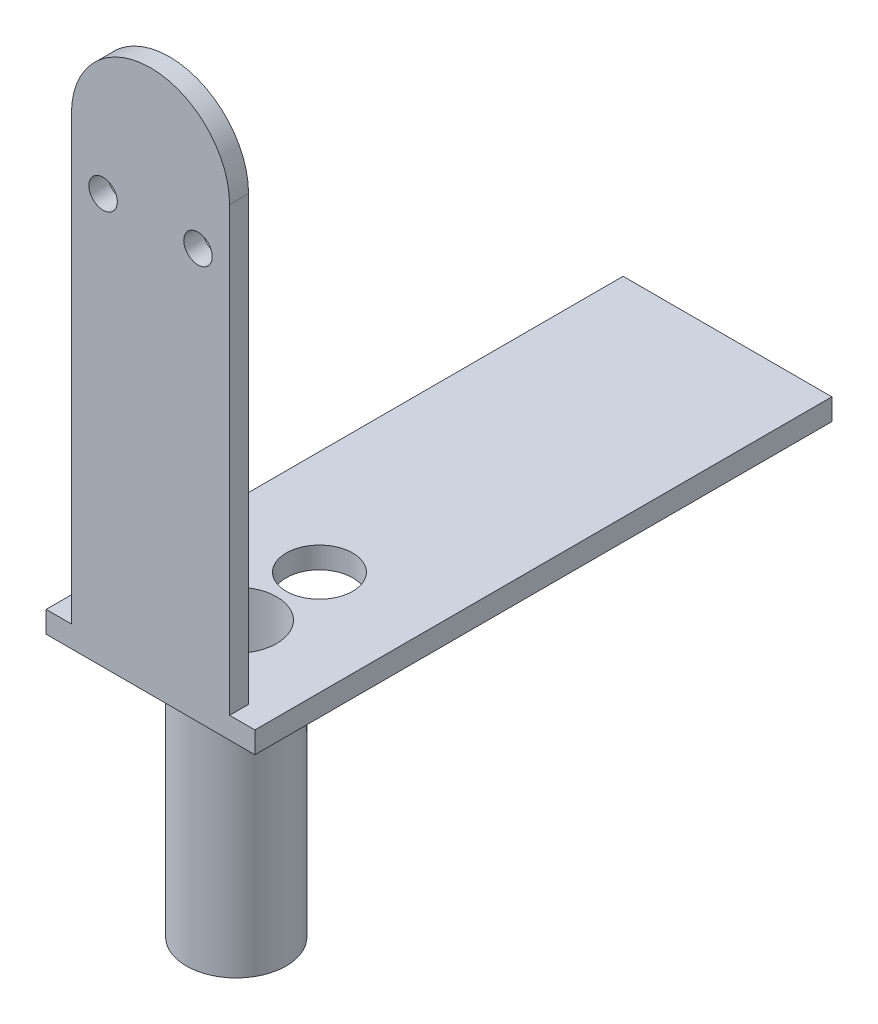
SolidWorks part; units mm, degrees
ref_plane "Front Plane" through (0, 0, 0) normal (0, 0, 1) x (1, 0, 0)
ref_plane "Top Plane" through (0, 0, 0) normal (0, 1, 0) x (1, 0, 0)
ref_plane "Right Plane" through (0, 0, 0) normal (1, 0, 0) x (0, 0, -1)
sketch "Sketch1" plane through (0, 0, 0) normal (0, 0, 1) x (1, 0, 0)
  line L0 (0, 0) -> (33, 0)
  line L1 (16.5, 0) -> (29, 0)
  line L2 (16.5, 0) -> (16.5, 9.4766)
  line L3 (4, 0) -> (4, 80.5)
  line L4 (29, 0) -> (29, 80.5)
  line L5 (0, 0) -> (0, 80.5)
  line L6 (0, 80.5) -> (4, 80.5)
  line L7 (33, 0) -> (33, 80.5)
  line L8 (33, 80.5) -> (29, 80.5)
  arc A0 (33, 80.5) -> (0, 80.5) centre (16.5, 80.5) ccw
  arc A1 (4, 80.5) -> (29, 80.5) centre (16.5, 80.5) cw
  point P5 (4, 0)
  dimension "D1" = 33
  dimension "D2" = 12.5
  dimension "D3" = 80.5
extrude "Boss-Extrude1" add sketch "Sketch1" along normal blind 71 contours L6 L5 L0 L3 | L6 A1 L8 A0 | L7 L8 L4 L0 region at (2, 40.25, 0) region at (16.5, 96.631, 0) region at (31, 40.25, 0)
sketch "Sketch2" plane through (0, 0, 71) normal (0, 0, 1) x (1, 0, 0)
  line L2 (33, 48.5) -> (0, 48.5)
  line L3 (0, 0) -> (0, 80.5) construction
  line L4 (0, 48.5) -> (0, 80.5)
  line L5 (33, 0) -> (33, 80.5) construction
  line L6 (33, 48.5) -> (33, 80.5)
  arc A0 (33, 80.5) -> (0, 80.5) centre (16.5, 80.5) ccw construction
  arc A1 (33, 80.5) -> (0, 80.5) centre (16.5, 80.5) ccw
  point P8 (16.5, 48.5)
extrude "Boss-Extrude2" add sketch "Sketch2" against normal blind 4
sketch "Sketch3" plane through (0, 0, 67) normal (0, 0, -1) x (-1, 0, 0)
  line L0 (-4, 48.5) -> (-29, 48.5) construction
  line L1 (-4, 48.5) -> (-29, 48.5)
  line L3 (-29, 44.5) -> (-4, 44.5)
  line L5 (0, 0) -> (0, 80.5) construction
  line L6 (0, 0) -> (0, 48.5)
  line L7 (-4, 48.5) -> (0, 48.5)
  line L8 (0, 0) -> (-3.8379, 0)
  line L9 (-4, 44.5) -> (-3.8379, 0)
  line L10 (-16.5, 44.5) -> (-16.5, 41.0104)
  line L11 (-33, 0) -> (-33, 48.5)
  line L12 (-29, 48.5) -> (-33, 48.5)
  line L13 (-29, 44.5) -> (-29.1621, 0)
  line L14 (-33, 0) -> (-29.1621, 0)
  line M8 (-29, 48.5) -> (-4, 48.5)
extrude "Boss-Extrude3" add sketch "Sketch3" against normal blind 34.2 contours L11 L14 L13 L3 L9 L8 L6 L7 L12 M8 region at (2, 47.9134, 67)
sketch "Sketch4" plane through (0, 0, 0) normal (0, 0, -1) x (-1, 0, 0)
  line L6 (-4, 80.5) -> (-4, 0)
  line L7 (-4, 0) -> (0, 0)
  line L8 (0, 0) -> (0, 80.5)
  line L9 (-33, 80.5) -> (-33, 0)
  line L10 (-33, 0) -> (-29, 0)
  line L11 (-29, 0) -> (-29, 80.5)
  line L12 (-4, 80.5) -> (-4, 0)
  line L13 (-4, 0) -> (0, 0)
  line L14 (0, 0) -> (0, 80.5)
  line L15 (-33, 80.5) -> (-33, 0)
  line L16 (-33, 0) -> (-29, 0)
  line L17 (-29, 0) -> (-29, 80.5)
  arc A2 (0, 80.5) -> (-33, 80.5) centre (-16.5, 80.5) ccw
  arc A3 (-4, 80.5) -> (-29, 80.5) centre (-16.5, 80.5) ccw
  arc A4 (0, 80.5) -> (-33, 80.5) centre (-16.5, 80.5) ccw
  arc A5 (-4, 80.5) -> (-29, 80.5) centre (-16.5, 80.5) ccw
  dimension "D1" = 0
extrude "Cut-Extrude1" cut sketch "Sketch4" against normal blind 13
sketch "Sketch5" plane through (0, 0, 71) normal (0, 0, 1) x (1, 0, 0)
  line L0 (0, 80.5) -> (33, 80.5)
  circle A0 centre (16.5, 80.5) radius 10
  dimension "D1" = 20
extrude "Cut-Extrude2" cut sketch "Sketch5" against normal blind 13 contours L0 A0 | L0 A0 region at (16.5, 84.7441, 71) region at (16.5, 76.2559, 71)
sketch "Sketch6" plane through (0, 0, 71) normal (0, 0, 1) x (1, 0, 0)
  line L0 (16.5, 70.5) -> (16.5, 73.1374)
  line L1 (16.5, 70.5) -> (33, 70.5)
  line L2 (33, 48.5) -> (33, 80.5) construction
  circle A0 centre (26.5, 70.5) radius 1.7
  circle A1 centre (6.5, 70.5) radius 1.7
  dimension "D2" = 3.4
  dimension "D1" = 6.5
extrude "Cut-Extrude3" cut sketch "Sketch6" against normal blind 13 contours A1 | L1 A0 | L1 A0 region at (26.5, 71.2215, 71) region at (26.5, 69.7785, 71) region at (6.5, 70.5, 71)
sketch "Sketch7" plane through (0, 0, 71) normal (0, 0, 1) x (1, 0, 0)
  circle A0 centre (6.5, 70.5) radius 3.25
  circle A1 centre (26.5, 70.5) radius 3.25
  dimension "D1" = 6.5
extrude "Cut-Extrude4" cut sketch "Sketch7" against normal blind 2.5
sketch "Sketch9" plane through (0, 0, 0) normal (0, -1, 0) x (1, 0, 0)
  line L0 (29.1621, 101.2) -> (29.1621, 71) construction
  line L1 (29.1621, 101.2) -> (29.1621, 71)
  line L2 (29.1621, 71) -> (29, 71)
  line L3 (29, 71) -> (29, 120)
  line L4 (29, 120) -> (29.1621, 101.2)
  line L6 (29, 67) -> (4, 67) construction
  line L7 (29, 67) -> (4, 67)
  line L8 (16.5, 67) -> (16.5, 71)
  line L9 (4, 120) -> (3.8379, 101.2)
  line L10 (4, 71) -> (4, 120)
  line L11 (3.8379, 71) -> (4, 71)
  line L12 (3.8379, 101.2) -> (3.8379, 71)
extrude "Boss-Extrude4" add sketch "Sketch9" against normal up to surface (44.5 mm away) contours L4 L1 L2 L3 | L9 L12 L11 L10 up to face at (16.5, 44.5, 79.7333)
sketch "Sketch10" plane through (0, 0, 101.2) normal (0, 0, 1) x (1, 0, 0)
  line L1 (40.2439, -6.5645) -> (-5.7585, -6.5645)
  line L2 (40.2439, -6.5645) -> (40.2439, 55.1467)
  line L3 (40.2439, 55.1467) -> (-5.7585, 55.1467)
  line L4 (-5.7585, -6.5645) -> (-5.7585, 55.1467)
  line L5 (40.2439, -6.5645) -> (-5.7585, 55.1467) construction
  line L6 (40.2439, 55.1467) -> (-5.7585, -6.5645) construction
  point P0 (17.2427, 24.2911)
extrude "Cut-Extrude5" cut sketch "Sketch10" along normal blind 42
fillet "Fillet1" radius 18 2 edges at (16.5, 44.5, 67) (16.5, 48.5, 71)
sketch "Sketch11" plane through (0, 0, 101.2) normal (0, 0, 1) x (1, 0, 0)
  line L0 (29, 0) -> (4, 0)
  line L8 (4, 44.5) -> (29, 44.5)
  line L9 (29, 44.5) -> (29, 0)
  line L10 (29, 0) -> (33, 0)
  line L11 (33, 0) -> (33, 48.5)
  line L12 (33, 48.5) -> (0, 48.5)
  line L13 (0, 48.5) -> (0, 0)
  line L14 (0, 0) -> (4, 0)
  line L15 (4, 0) -> (4, 44.5)
  line L18 (29, 0) -> (33, 0)
  line L19 (33, 0) -> (33, 48.5)
  line L20 (33, 48.5) -> (0, 48.5)
  line L21 (0, 48.5) -> (0, 0)
  line L22 (0, 0) -> (4, 0)
  dimension "D1" = 0
extrude "Boss-Extrude5" add sketch "Sketch11" along normal blind 4
fillet "Fillet3" radius 16.2 1 edges at (16.5, 48.5, 105.2)
fillet "Fillet4" radius 14 1 edges at (16.5, 44.5, 101.2)
sketch "Sketch12" plane through (0, 0, 0) normal (0, -1, 0) x (1, 0, 0)
  line L8 (4, 13) -> (4, 101.2)
  line L9 (4, 101.2) -> (29, 101.2)
  line L10 (29, 101.2) -> (29, 13)
  line L11 (29, 13) -> (33, 13)
  line L12 (33, 13) -> (33, 105.2)
  line L13 (33, 105.2) -> (0, 105.2)
  line L14 (0, 105.2) -> (0, 13)
  line L15 (0, 13) -> (4, 13)
  line L16 (4, 13) -> (4, 101.2)
  line L17 (4, 101.2) -> (29, 101.2)
  line L18 (29, 101.2) -> (29, 13)
  line L19 (29, 13) -> (33, 13)
  line L20 (33, 13) -> (33, 105.2)
  line L21 (33, 105.2) -> (0, 105.2)
  line L22 (0, 105.2) -> (0, 13)
  line L23 (0, 13) -> (4, 13)
  dimension "D1" = 0
extrude "Cut-Extrude6" cut sketch "Sketch12" against normal blind 10.6
sketch "Sketch13" plane through (0, 0, 13) normal (0, 0, -1) x (-1, 0, 0)
  line L6 (-33, 80.5) -> (-33, 10.6)
  line L7 (-33, 10.6) -> (-29, 10.6)
  line L8 (-29, 10.6) -> (-29, 80.5)
  line L9 (-4, 80.5) -> (-4, 10.6)
  line L10 (-4, 10.6) -> (0, 10.6)
  line L11 (0, 10.6) -> (0, 80.5)
  line L12 (-33, 80.5) -> (-33, 10.6)
  line L13 (-33, 10.6) -> (-29, 10.6)
  line L14 (-29, 10.6) -> (-29, 80.5)
  line L15 (-4, 80.5) -> (-4, 10.6)
  line L16 (-4, 10.6) -> (0, 10.6)
  line L17 (0, 10.6) -> (0, 80.5)
  arc A2 (-4, 80.5) -> (-29, 80.5) centre (-16.5, 80.5) ccw
  arc A3 (0, 80.5) -> (-33, 80.5) centre (-16.5, 80.5) ccw
  arc A4 (-4, 80.5) -> (-29, 80.5) centre (-16.5, 80.5) ccw
  arc A5 (0, 80.5) -> (-33, 80.5) centre (-16.5, 80.5) ccw
  dimension "D1" = 0
extrude "Boss-Extrude6" add sketch "Sketch13" along normal blind 4
ref_plane "Plane1" through (0, 0, 13) normal (0, 0, -1) x (-1, 0, 0)
sketch "Sketch14" plane through (0, 0, 13) normal (0, 0, -1) x (-1, 0, 0)
  line L0 (-29, 10.6) -> (-4, 10.6)
  line L6 (-33, 80.5) -> (-33, 10.6)
  line L7 (-33, 10.6) -> (-29, 10.6)
  line L8 (-29, 10.6) -> (-29, 80.5)
  line L9 (-4, 80.5) -> (-4, 10.6)
  line L10 (-4, 10.6) -> (0, 10.6)
  line L11 (0, 10.6) -> (0, 80.5)
  line L12 (-33, 80.5) -> (-33, 10.6)
  line L13 (-33, 10.6) -> (-29, 10.6)
  line L16 (-4, 10.6) -> (0, 10.6)
  line L17 (0, 10.6) -> (0, 80.5)
  arc A2 (0, 80.5) -> (-33, 80.5) centre (-16.5, 80.5) ccw
  arc A3 (-4, 80.5) -> (-29, 80.5) centre (-16.5, 80.5) ccw
  arc A4 (0, 80.5) -> (-33, 80.5) centre (-16.5, 80.5) ccw
  dimension "D1" = 0
extrude "Cut-Extrude7" cut sketch "Sketch14" against normal blind 148
sketch "Sketch15" plane through (0, 0, 13) normal (0, 0, 1) x (1, 0, 0)
  line L0 (4, 10.6) -> (29, 10.6)
  line L6 (29, 80.5) -> (29, 10.6)
  line L7 (29, 10.6) -> (33, 10.6)
  line L8 (33, 10.6) -> (33, 80.5)
  line L9 (0, 80.5) -> (0, 10.6)
  line L10 (0, 10.6) -> (4, 10.6)
  line L11 (4, 10.6) -> (4, 80.5)
  line L12 (29, 80.5) -> (29, 10.6)
  line L13 (29, 10.6) -> (33, 10.6)
  line L17 (4, 10.6) -> (4, 80.5)
  arc A2 (33, 80.5) -> (0, 80.5) centre (16.5, 80.5) ccw
  arc A3 (29, 80.5) -> (4, 80.5) centre (16.5, 80.5) ccw
  arc A5 (29, 80.5) -> (4, 80.5) centre (16.5, 80.5) ccw
  line M10 (29, 80.5) -> (29, 10.6)
  line M16 (4, 10.6) -> (4, 80.5)
  arc M17 (4, 80.5) -> (29, 80.5) centre (16.5, 80.5) cw
  dimension "D1" = 0
extrude "Boss-Extrude7" add sketch "Sketch15" along normal blind 3 separate body contours L0 M16 M10 M17 region at (16.5, 50.5076, 13)
sketch "Sketch16" plane through (0, 0, 9) normal (0, 0, -1) x (-1, 0, 0)
  line L6 (-33, 80.5) -> (-33, 10.6)
  line L7 (-33, 10.6) -> (-29, 10.6)
  line L8 (-29, 10.6) -> (-29, 80.5)
  line L9 (-4, 80.5) -> (-4, 10.6)
  line L10 (-4, 10.6) -> (0, 10.6)
  line L11 (0, 10.6) -> (0, 80.5)
  line L12 (-33, 80.5) -> (-33, 10.6)
  line L13 (-33, 10.6) -> (-29, 10.6)
  line L14 (-29, 10.6) -> (-29, 80.5)
  line L15 (-4, 80.5) -> (-4, 10.6)
  line L16 (-4, 10.6) -> (0, 10.6)
  line L17 (0, 10.6) -> (0, 80.5)
  arc A2 (0, 80.5) -> (-33, 80.5) centre (-16.5, 80.5) ccw
  arc A3 (-4, 80.5) -> (-29, 80.5) centre (-16.5, 80.5) ccw
  arc A4 (0, 80.5) -> (-33, 80.5) centre (-16.5, 80.5) ccw
  arc A5 (-4, 80.5) -> (-29, 80.5) centre (-16.5, 80.5) ccw
  dimension "D1" = 0
extrude "Cut-Extrude8" cut sketch "Sketch16" against normal blind 14
sketch "Sketch17" plane through (0, 0, 13) normal (0, 0, -1) x (-1, 0, 0)
  line L0 (-16.5, 93) -> (-16.5, 68)
  line L1 (-16.5, 68) -> (-4, 68)
  line L2 (-4, 10.6) -> (-4, 80.5) construction
  arc A0 (-4, 80.5) -> (-29, 80.5) centre (-16.5, 80.5) ccw construction
  circle A1 centre (-9, 72) radius 2.25
  circle A2 centre (-24, 72) radius 2.25
  dimension "D2" = 4.5
  dimension "D3" = 5
  dimension "D4" = 4
  dimension "D1" = 25
extrude "Cut-Extrude9" cut sketch "Sketch17" against normal blind 14 contours A2 | A1 region at (24, 72, 13)
sketch "Sketch18" plane through (0, 10.6, 0) normal (0, -1, 0) x (1, 0, 0)
  line L0 (29, 16) -> (29, -76.2)
  line L1 (29, 16) -> (4, 16)
  line L2 (4, 16) -> (4, -76.2)
  line L3 (4, -76.2) -> (29, -76.2)
  dimension "D1" = 92.2
extrude "Boss-Extrude8" add sketch "Sketch18" along normal blind 4
sketch "Sketch19" plane through (0, 6.6, 0) normal (0, -1, 0) x (1, 0, 0)
  line L0 (4, 16) -> (0, 16)
  line L1 (0, 16) -> (0, -76.2)
  line L2 (4, -76.2) -> (0, -76.2)
  line L3 (4, -76.2) -> (4, 16)
  line L4 (16.5, 16) -> (16.5, 9.1971)
  line L5 (29, 16) -> (4, 16) construction
  line L6 (29, -76.2) -> (33, -76.2)
  line L7 (33, 16) -> (33, -76.2)
  line L8 (29, 16) -> (33, 16)
  line L9 (29, -76.2) -> (29, 16)
  line M7 (4, 16) -> (4, -76.2)
  line M9 (29, -76.2) -> (29, 16)
extrude "Boss-Extrude9" add sketch "Sketch19" against normal up to surface (4 mm away) contours L2 L0 L1 M7 | L8 L6 L7 M9 region at (2, 6.6, -30.1) region at (31, 6.6, -30.1) up to face at (16.5, 10.6, -31.6)
sketch "Sketch20" plane through (0, 6.6, 0) normal (0, -1, 0) x (1, 0, 0)
  line L0 (16.5, 16) -> (16.5, -10.7)
  line L1 (33, 16) -> (0, 16) construction
  circle A0 centre (16.5, -10.7) radius 5.25
  dimension "D2" = 10.5
  dimension "D1" = 26.7
extrude "Cut-Extrude10" cut sketch "Sketch20" against normal up to surface (4 mm away) contours A0 region at (12.8927, 6.6, -14.3073) up to face at (16.5, 10.6, -7.8)
sketch "Sketch21" plane through (0, 6.6, 0) normal (0, -1, 0) x (1, 0, 0)
  line L4 (33, 16) -> (0, 16)
  line L5 (0, 16) -> (0, -76.2)
  line L6 (0, -76.2) -> (33, -76.2)
  line L7 (33, -76.2) -> (33, 16)
  line L8 (33, 16) -> (0, 16)
  line L9 (0, 16) -> (0, -76.2)
  line L10 (0, -76.2) -> (33, -76.2)
  line L11 (33, -76.2) -> (33, 16)
  dimension "D1" = 0
extrude "Cut-Extrude11" cut sketch "Sketch21" against normal blind 0.6
sketch "Sketch22" plane through (0, 7.2, 0) normal (0, -1, 0) x (1, 0, 0)
  line L0 (16.5, 16) -> (16.5, 1.3)
  line L1 (33, 16) -> (0, 16) construction
  circle A0 centre (16.5, 1.3) radius 5.25
  dimension "D2" = 10.5
  dimension "D1" = 14.7
extrude "Cut-Extrude12" cut sketch "Sketch22" against normal up to surface (3.4 mm away) contours A0 region at (12.8927, 7.2, -2.3073) up to face at (16.5, 10.6, -15.95)
sketch "Sketch23" plane through (0, 7.2, 0) normal (0, -1, 0) x (1, 0, 0)
  line L0 (16.5, -5.45) -> (16.5, 10.35)
  circle A0 centre (16.5, -10.7) radius 5.25 construction
  circle A1 centre (16.5, 2.45) radius 7.9
  circle A2 centre (16.5, 2.45) radius 6.4
  dimension "D1" = 15.8
extrude "Boss-Extrude10" add sketch "Sketch23" along normal blind 40 contours A2 L0 A1 | A2 L0 A1 region at (8.7766, 7.2, 2.45) region at (16.6766, 7.2, -4.7)
sketch "Sketch24" plane through (0, 7.2, 0) normal (0, -1, 0) x (1, 0, 0)
  circle A2 centre (16.5, 2.45) radius 6.4 construction
  circle A3 centre (16.5, 2.45) radius 6.4
extrude "Cut-Extrude13" cut sketch "Sketch24" against normal up to surface (3.4 mm away) up to face at (16.5, 10.6, -3.95)
sketch "Sketch25" plane through (0, 10.6, 0) normal (0, 1, 0) x (1, 0, 0)
  line L0 (16.5, 76.2) -> (16.5, 74.7)
  line L1 (0, 76.2) -> (33, 76.2) construction
  line L2 (16.5, 74.7) -> (6.5, 74.7)
  line L3 (6.5, 74.7) -> (6.5, 72.7)
  line L4 (16.5, 74.7) -> (26.5, 74.7)
  line L5 (26.5, 74.7) -> (26.5, 72.7)
  line L6 (26.5, 72.7) -> (6.5, 72.7)
extrude "Boss-Extrude11" add sketch "Sketch25" along normal blind 15 contours L6 L5 L4 L2 L3 region at (16.5, 10.6, -73.7)
sketch "Sketch26" plane through (0, 10.6, 0) normal (0, 1, 0) x (1, 0, 0)
  line L0 (21.5, 74.7) -> (11.5, 74.7)
  line L1 (6.5, 74.7) -> (26.5, 74.7) construction
  line L2 (11.5, 74.7) -> (16.5, 74.7)
  line L3 (11.5, 74.7) -> (11.5, 76.2)
  line L4 (0, 76.2) -> (33, 76.2) construction
  line L5 (11.5, 76.2) -> (21.5, 76.2)
  line L6 (21.5, 76.2) -> (21.5, 74.7)
  point P5 (16.5, 74.7)
  dimension "D1" = 10
extrude "Boss-Extrude12" add sketch "Sketch26" along normal up to surface (15 mm away) contours L3 L5 L6 L0 up to face at (16.5, 25.6, -73.7)
sketch "Sketch27" plane through (0, 10.6, 0) normal (0, 1, 0) x (1, 0, 0)
  line L8 (6.5, 72.7) -> (26.5, 72.7)
  line L9 (26.5, 72.7) -> (26.5, 74.7)
  line L10 (26.5, 74.7) -> (21.5, 74.7)
  line L11 (21.5, 74.7) -> (21.5, 76.2)
  line L12 (21.5, 76.2) -> (11.5, 76.2)
  line L13 (11.5, 76.2) -> (11.5, 74.7)
  line L14 (11.5, 74.7) -> (6.5, 74.7)
  line L15 (6.5, 74.7) -> (6.5, 72.7)
  line L16 (6.5, 72.7) -> (26.5, 72.7)
  line L17 (26.5, 72.7) -> (26.5, 74.7)
  line L18 (26.5, 74.7) -> (21.5, 74.7)
  line L19 (21.5, 74.7) -> (21.5, 76.2)
  line L20 (21.5, 76.2) -> (11.5, 76.2)
  line L21 (11.5, 76.2) -> (11.5, 74.7)
  line L22 (11.5, 74.7) -> (6.5, 74.7)
  line L23 (6.5, 74.7) -> (6.5, 72.7)
  dimension "D1" = 0
extrude "Cut-Extrude14" cut sketch "Sketch27" along normal blind 36
sketch "Sketch28" plane through (0, 0, -76.2) normal (0, 0, -1) x (-1, 0, 0)
  line L4 (0, 10.6) -> (-33, 10.6)
  line L5 (-33, 10.6) -> (-33, 7.2)
  line L6 (-33, 7.2) -> (0, 7.2)
  line L7 (0, 7.2) -> (0, 10.6)
  line L8 (0, 10.6) -> (-33, 10.6)
  line L9 (-33, 10.6) -> (-33, 7.2)
  line L10 (-33, 7.2) -> (0, 7.2)
  line L11 (0, 7.2) -> (0, 10.6)
  dimension "D1" = 0
extrude "Cut-Extrude15" cut sketch "Sketch28" against normal blind 1
